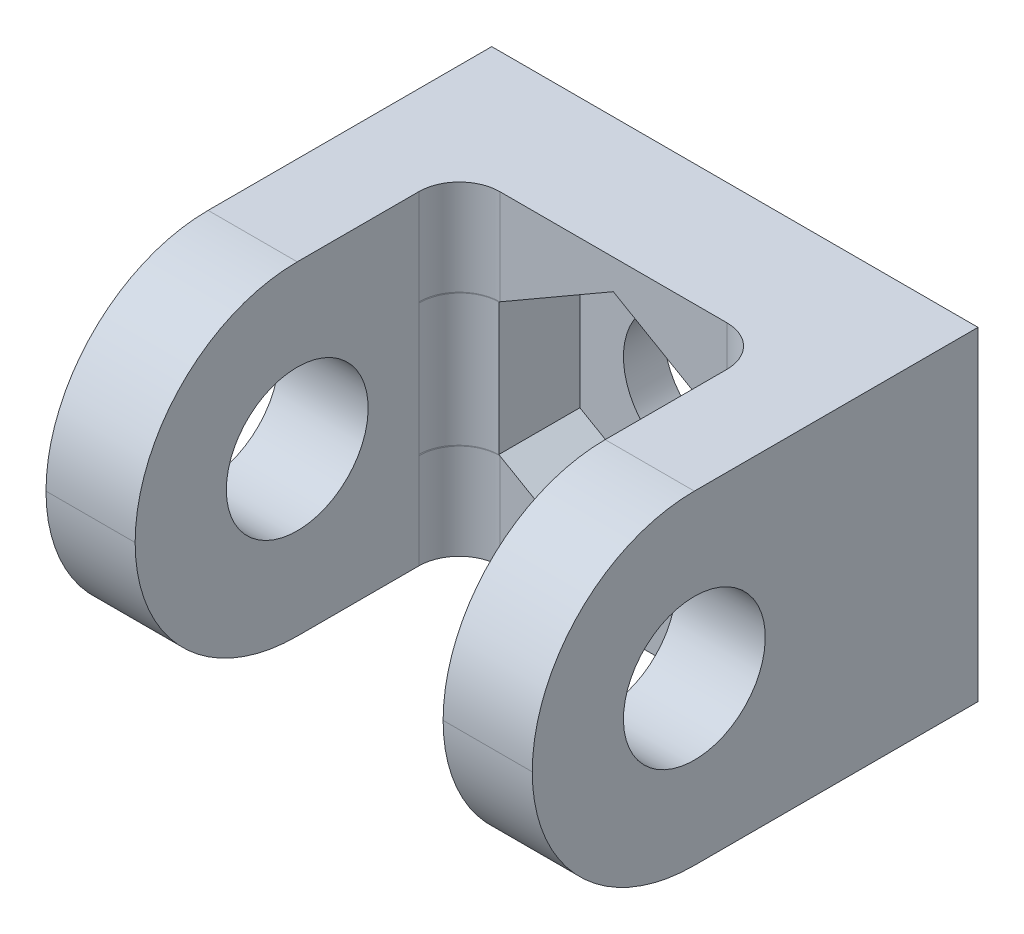
SolidWorks part; units mm, degrees
ref_plane "Спереди" through (0, 0, 0) normal (0, 0, 1) x (1, 0, 0)
ref_plane "Сверху" through (0, 0, 0) normal (0, 1, 0) x (1, 0, 0)
ref_plane "Справа" through (0, 0, 0) normal (1, 0, 0) x (0, 0, -1)
sketch "Эскиз1" plane through (0, 0, 0) normal (0, 0, 1) x (1, 0, 0)
  line L1 (-6, 4) -> (6, 4)
  line L2 (-6, 4) -> (-6, -4)
  line L3 (-6, -4) -> (6, -4)
  line L4 (6, 4) -> (6, -4)
  line L5 (-6, 4) -> (6, -4) construction
  line L6 (-6, -4) -> (6, 4) construction
  point P0 (0, 0)
  point P6 (0, 0)
  dimension "D1" = 12
  dimension "D2" = 8
extrude "Бобышка-Вытянуть1" add sketch "Эскиз1" along normal blind 3
sketch "Эскиз2" plane through (0, 0, 3) normal (0, 0, 1) x (1, 0, 0)
  line L1 (2.825, -1.631) -> (2.825, 1.631)
  line L2 (2.825, 1.631) -> (0, 3.262)
  line L3 (0, 3.262) -> (-2.825, 1.631)
  line L4 (-2.825, 1.631) -> (-2.825, -1.631)
  line L5 (-2.825, -1.631) -> (0, -3.262)
  line L6 (0, -3.262) -> (2.825, -1.631)
  circle A0 centre (0, 0) radius 2.825 construction
  dimension "D1" = 5.65
extrude "Вырез-Вытянуть1" cut sketch "Эскиз2" against normal blind 2
sketch "Эскиз3" plane through (0, 0, 1) normal (0, 0, 1) x (1, 0, 0)
  circle A0 centre (0, 0) radius 1.75
extrude "Вырез-Вытянуть2" cut sketch "Эскиз3" against normal blind 2
sketch "Эскиз4" plane through (0, 0, 3) normal (0, 0, 1) x (1, 0, 0)
  line L0 (-6, -4) -> (6, -4) construction
  line L1 (-6, 4) -> (-3.8, 4)
  line L2 (-6, 4) -> (-6, -4)
  line L3 (-6, -4) -> (-3.8, -4)
  line L4 (-3.8, 4) -> (-3.8, -4)
  line L6 (6, 4) -> (3.8, 4)
  line L7 (6, 4) -> (6, -4)
  line L8 (6, -4) -> (3.8, -4)
  line L9 (3.8, 4) -> (3.8, -4)
  dimension "D1" = 2.2
  dimension "D2" = 2.2
extrude "Бобышка-Вытянуть2" add sketch "Эскиз4" along normal blind 8
fillet "Скругление1" radius 4 4 edges at (4.9, 4, 11) (-4.9, 4, 11) (4.9, -4, 11) (-4.9, -4, 11)
sketch "Эскиз5" plane through (6, 0, 0) normal (1, 0, 0) x (0, 0, -1)
  line L0 (-7, 4) -> (-7, -4.5119) construction
  line L1 (0, 0) -> (-11.9819, 0) construction
  line L2 (0, -4) -> (0, 4) construction
  circle A0 centre (-7, 0) radius 1.75
extrude "Вырез-Вытянуть3" cut sketch "Эскиз5" against normal through all
fillet "Скругление2" radius 1 2 edges at (-3.8, 0, 3) (3.8, 0, 3)
equation "\"D2@Эскиз4\"=\"D1@Эскиз4\""
